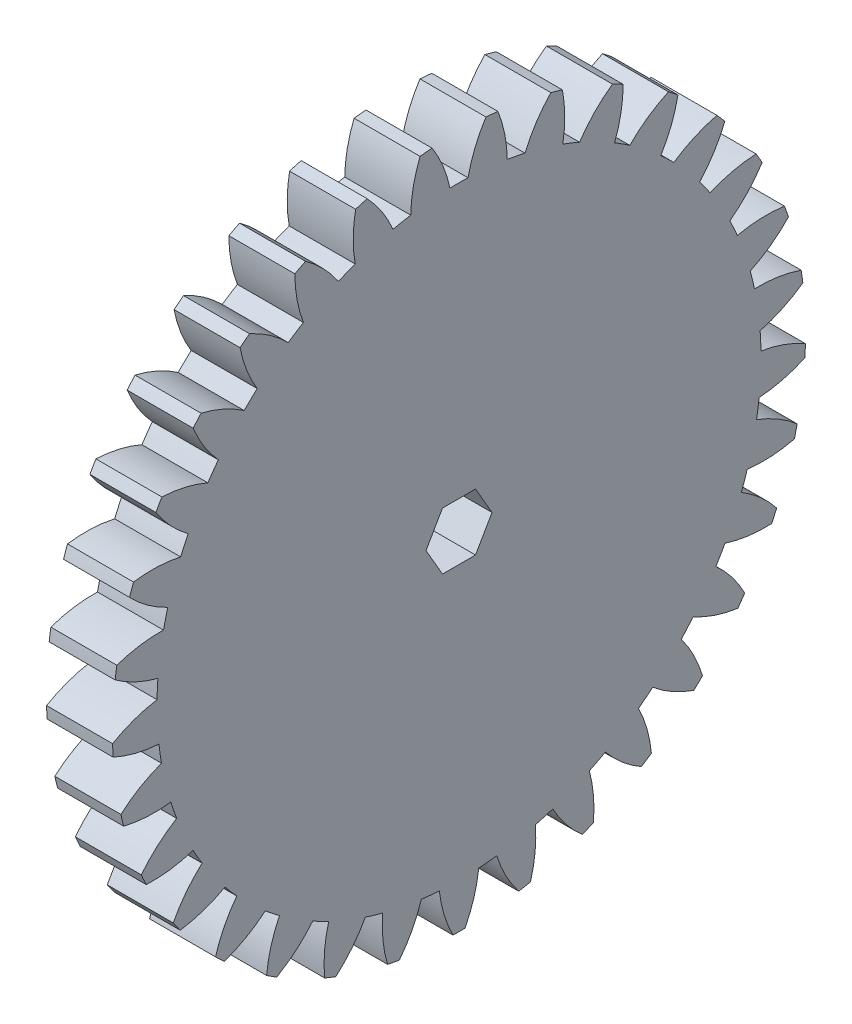
SolidWorks part; units mm, degrees
ref_plane "Plane1" through (0, 0, 0) normal (0, 0, 1) x (1, 0, 0)
ref_plane "Plane2" through (0, 0, 0) normal (0, 1, 0) x (1, 0, 0)
ref_plane "Plane3" through (0, 0, 0) normal (1, 0, 0) x (0, 0, -1)
sketch "HoldingSke" plane through (0, 0, 0) normal (0, 1, 0) x (1, 0, 0)
  line L0 (0, 0) -> (0.5591, -0.3631)
  line L1 (-15, 0) -> (100, 0) construction
  line L2 (0, 0) -> (-2.1039, 2.3779)
  line L3 (0, 0) -> (-11.863, 4.5341)
  line L4 (0, 0) -> (7.2428, 4.7035)
  line L5 (0, 0) -> (-46.8476, -17.4728)
  line L6 (0, 0) -> (-4.1448, -2.7965)
  line L7 (-2.1039, 2.3779) -> (8.6586, 51.2059)
  line L8 (-76.2, 54.61) -> (-75.3, 54.61)
  line L9 (-71.009, 38.7566) -> (-53.1078, 45.2721)
  line L10 (-76.2, 71.12) -> (104.1128, 71.12)
  line L11 (0, 0) -> (-5, 0)
  line L12 (-76.2, 101.6) -> (-76.147, 101.6)
  line L13 (24.9733, 27.94) -> (52.9518, 28.4284)
  line L14 (24.9733, 27.94) -> (24.9743, 27.94)
  line L15 (24.9733, 27.94) -> (100.4006, 29.5858)
  line L16 (-63.627, -1.5) -> (-12.827, -1.5)
  circle A0 centre (0, 0) radius 2.5
  circle A1 centre (0, 0) radius 22.874
  circle A2 centre (0, 0) radius 37.5
  circle A3 centre (0, 0) radius 2.5
  dimension "MHD" = 45.748
  dimension "Hub_dia" = 75
  dimension "Bore" = 5
  dimension "MBD" = 5
  dimension "Num_teeth" = 33
  dimension "Pitch" = 0.6667
  dimension "Overall_len" = 50
  dimension "Show_teeth" = 33
  dimension "Thickness" = 5
  dimension "OAL" = 50.0001
  dimension "T_dim" = 0.9
  dimension "Ap" = 20
  dimension "H" = 19.05
  dimension "Pitch_radius" = 180.3128
  dimension "Width" = 5
  dimension "Backlash" = 0.053
  dimension "Addendum_fac" = 1
  dimension "Dedendum_fac" = 1.25
  dimension "Clearance_fac" = 0.25
  dimension "Dedendum_add" = 0.001
  dimension "Module" = 1.5
sketch "BasProSke" plane through (0, 0, 0) normal (0, 1, 0) x (1, 0, 0)
  line L0 (-10, 0) -> (60, 0) construction
  line L1 (0, 0) -> (0, 26.25)
  line L2 (0, 0) -> (5, 0)
  line L3 (5, 0) -> (5, 26.25)
  line L4 (5, 26.25) -> (0, 26.25)
  dimension "Thickness" = 5
  dimension "Diameter" = 52.5
revolve "Base-Revolve" add sketch "BasProSke" angle 360 about L0
sketch "TooCutSke" plane through (0, 0, 0) normal (1, 0, 0) x (0, 0, -1)
  line L1 (0, 0) -> (0, 107) construction
  line L2 (0, 0) -> (-1.2704, 24.7174) construction
  line L3 (0, 0) -> (-4.7008, 49.2285) construction
  line L4 (-1.2704, 24.7174) -> (-2.3504, 24.6142) construction
  arc A0 (0.6837, 22.8638) -> (-0.6837, 22.8638) centre (0, 0) ccw
  arc A1 (2.0575, 26.1947) -> (-2.0575, 26.1947) centre (0, 0) ccw
  circle A2 centre (0, 0) radius 24.75 construction
  circle A3 centre (0, 0) radius 23.2574 construction
  arc A4 (-0.6837, 22.8638) -> (-2.0575, 26.1947) centre (-10.3699, 20.8176) ccw
  arc A5 (2.0575, 26.1947) -> (0.6837, 22.8638) centre (10.3699, 20.8176) ccw
  dimension "Root_dia" = 45.748
  dimension "Overcut_dia" = 52.5508
  dimension "Pitch_dia" = 49.5
  dimension "Base_dia" = 46.5148
  dimension "Flank_rad" = 9.9
  dimension "Half_ang" = 5.455
  dimension "Half_CT" = 1.0849
extrude "ToothCut" cut sketch "TooCutSke" along normal through all
fillet "Breaks" [suppressed] radius 0.03 tangent propagation no
fillet "RootFillets" [suppressed] radius 0.376
pattern_circular "TeethCuts" count 33 every 10.909 about axis through (-10, 0, 0) along (1, 0, 0) of "ToothCut", "RootFillets", "Breaks"
sketch "HubNeaOneSke" plane through (0, 0, 0) normal (-1, 0, 0) x (0, 0, 1)
  circle A0 centre (0, 0) radius 22.874
  dimension "Diameter" = 45.748
extrude "HubNearOne" [suppressed] add sketch "HubNeaOneSke" along normal blind 45.0001
sketch "HubNeaBotSke" plane through (0, 0, 0) normal (-1, 0, 0) x (0, 0, 1)
  circle A0 centre (0, 0) radius 22.874
  dimension "Diameter" = 45.748
extrude "HubNearBoth" [suppressed] add sketch "HubNeaBotSke" along normal blind 22.5
ref_plane "FarPln" through (5, 0, 0) normal (1, 0, 0) x (0, 0, -1)
sketch "HubFarSke" plane through (5, 0, 0) normal (1, 0, 0) x (0, 0, -1)
  circle A0 centre (0, 0) radius 22.874
  dimension "Diameter" = 45.748
extrude "HubFar" [suppressed] add sketch "HubFarSke" along normal blind 22.5
sketch "BorSke" plane through (0, 0, 0) normal (1, 0, 0) x (0, 0, -1)
  line L1 (-2.5, 0) -> (-1.25, -2.1651)
  line L2 (-1.25, -2.1651) -> (1.25, -2.1651)
  line L3 (1.25, -2.1651) -> (2.5, 0)
  line L4 (2.5, 0) -> (1.25, 2.1651)
  line L5 (1.25, 2.1651) -> (-1.25, 2.1651)
  line L6 (-1.25, 2.1651) -> (-2.5, 0)
  circle A0 centre (0, 0) radius 2.5 construction
  circle A1 centre (0, 0) radius 2.1651 construction
  point P2 (-2.5, 0)
  dimension "Diameter" = 5
extrude "Bore" cut sketch "BorSke" along normal mid plane 100.0001
sketch "KeySke" plane through (0, 0, 0) normal (1, 0, 0) x (0, 0, -1)
  line L0 (-1, 0) -> (-1, 3.4)
  line L1 (-1, 3.4) -> (1, 3.4)
  line L2 (1, 3.4) -> (1, 0)
  line L3 (0, 0) -> (0, 34) construction
  line L4 (-1, 0) -> (1, 0)
  dimension "Offset" = 3.4
  dimension "Width" = 2
extrude "Keyway" [suppressed] cut sketch "KeySke" along normal mid plane 100.0001
pattern_circular "Keyway2" [suppressed] count 2 every 90 about axis through (-10, 0, 0) along (1, 0, 0) reverse direction yes
sketch "Sketch1" plane through (0, 0, 0) normal (-1, 0, 0) x (0, 0, 1)
  line L0 (-1.25, -2.1651) -> (1.25, -2.1651) construction
  line L1 (-2.5, 0) -> (-1.25, -2.1651) construction
  line L2 (-1.25, 2.1651) -> (-2.5, 0) construction
  line L3 (1.25, 2.1651) -> (-1.25, 2.1651) construction
  line L4 (2.5, 0) -> (1.25, 2.1651) construction
  line L5 (1.25, -2.1651) -> (2.5, 0) construction
  line L6 (2.5, 0) -> (1.25, 2.1651)
  line L7 (1.25, 2.1651) -> (-1.25, 2.1651)
  line L8 (-1.25, 2.1651) -> (-2.5, 0)
  line L9 (-2.5, 0) -> (-1.25, -2.1651)
  line L10 (-1.25, -2.1651) -> (1.25, -2.1651)
  line L11 (1.25, -2.1651) -> (2.5, 0)
  arc A40 (0.1868, -8.9981) -> (0.8757, -5.5554) centre (-1.8542, -6.7994) ccw
  arc A41 (-0.1868, -8.9981) -> (0.1868, -8.9981) centre (0, 0) ccw
  arc A42 (-0.8757, -5.5554) -> (-0.1868, -8.9981) centre (1.8542, -6.7994) ccw
  arc A43 (-2.5569, -5.0091) -> (-0.8757, -5.5554) centre (0, 0) ccw
  arc A44 (-5.1378, -7.3894) -> (-2.5569, -5.0091) centre (-5.4967, -4.4109) ccw
  arc A45 (-5.4401, -7.1698) -> (-5.1378, -7.3894) centre (0, 0) ccw
  arc A46 (-3.9738, -3.9797) -> (-5.4401, -7.1698) centre (-2.4965, -6.5907) ccw
  arc A47 (-5.0129, -2.5496) -> (-3.9738, -3.9797) centre (0, 0) ccw
  arc A48 (-8.4999, -2.9582) -> (-5.0129, -2.5496) centre (-7.0396, -0.3377) ccw
  arc A49 (-8.6154, -2.6029) -> (-8.4999, -2.9582) centre (0, 0) ccw
  arc A50 (-5.5541, -0.8839) -> (-8.6154, -2.6029) centre (-5.8936, -3.8646) ccw
  arc A51 (-5.5541, 0.8839) -> (-5.5541, -0.8839) centre (0, 0) ccw
  arc A52 (-8.6154, 2.6029) -> (-5.5541, 0.8839) centre (-5.8936, 3.8646) ccw
  arc A53 (-8.4999, 2.9582) -> (-8.6154, 2.6029) centre (0, 0) ccw
  arc A54 (-5.0129, 2.5496) -> (-8.4999, 2.9582) centre (-7.0396, 0.3377) ccw
  arc A55 (-3.9738, 3.9797) -> (-5.0129, 2.5496) centre (0, 0) ccw
  arc A56 (-5.4401, 7.1698) -> (-3.9738, 3.9797) centre (-2.4965, 6.5907) ccw
  arc A57 (-5.1378, 7.3894) -> (-5.4401, 7.1698) centre (0, 0) ccw
  arc A58 (-2.5569, 5.0091) -> (-5.1378, 7.3894) centre (-5.4967, 4.4109) ccw
  arc A59 (-0.8757, 5.5554) -> (-2.5569, 5.0091) centre (0, 0) ccw
  arc A60 (-0.1868, 8.9981) -> (-0.8757, 5.5554) centre (1.8542, 6.7994) ccw
  arc A61 (0.1868, 8.9981) -> (-0.1868, 8.9981) centre (0, 0) ccw
  arc A62 (0.8757, 5.5554) -> (0.1868, 8.9981) centre (-1.8542, 6.7994) ccw
  arc A63 (2.5569, 5.0091) -> (0.8757, 5.5554) centre (0, 0) ccw
  arc A64 (5.1378, 7.3894) -> (2.5569, 5.0091) centre (5.4967, 4.4109) ccw
  arc A65 (5.4401, 7.1698) -> (5.1378, 7.3894) centre (0, 0) ccw
  arc A66 (3.9738, 3.9797) -> (5.4401, 7.1698) centre (2.4965, 6.5907) ccw
  arc A67 (5.0129, 2.5496) -> (3.9738, 3.9797) centre (0, 0) ccw
  arc A68 (8.4999, 2.9582) -> (5.0129, 2.5496) centre (7.0396, 0.3377) ccw
  arc A69 (8.6154, 2.6029) -> (8.4999, 2.9582) centre (0, 0) ccw
  arc A70 (5.5541, 0.8839) -> (8.6154, 2.6029) centre (5.8936, 3.8646) ccw
  arc A71 (5.5541, -0.8839) -> (5.5541, 0.8839) centre (0, 0) ccw
  arc A72 (8.6154, -2.6029) -> (5.5541, -0.8839) centre (5.8936, -3.8646) ccw
  arc A73 (8.4999, -2.9582) -> (8.6154, -2.6029) centre (0, 0) ccw
  arc A74 (5.0129, -2.5496) -> (8.4999, -2.9582) centre (7.0396, -0.3377) ccw
  arc A75 (3.9738, -3.9797) -> (5.0129, -2.5496) centre (0, 0) ccw
  arc A76 (5.4401, -7.1698) -> (3.9738, -3.9797) centre (2.4965, -6.5907) ccw
  arc A77 (5.1378, -7.3894) -> (5.4401, -7.1698) centre (0, 0) ccw
  arc A78 (2.5569, -5.0091) -> (5.1378, -7.3894) centre (5.4967, -4.4109) ccw
  arc A79 (0.8757, -5.5554) -> (2.5569, -5.0091) centre (0, 0) ccw
  arc A80 (0.1868, -8.9981) -> (0.8757, -5.5554) centre (-1.8542, -6.7994) ccw
  arc A81 (-0.1868, -8.9981) -> (0.1868, -8.9981) centre (0, 0) ccw
  arc A82 (-0.8757, -5.5554) -> (-0.1868, -8.9981) centre (1.8542, -6.7994) ccw
  arc A83 (-2.5569, -5.0091) -> (-0.8757, -5.5554) centre (0, 0) ccw
  arc A84 (-5.1378, -7.3894) -> (-2.5569, -5.0091) centre (-5.4967, -4.4109) ccw
  arc A85 (-5.4401, -7.1698) -> (-5.1378, -7.3894) centre (0, 0) ccw
  arc A86 (-3.9738, -3.9797) -> (-5.4401, -7.1698) centre (-2.4965, -6.5907) ccw
  arc A87 (-5.0129, -2.5496) -> (-3.9738, -3.9797) centre (0, 0) ccw
  arc A88 (-8.4999, -2.9582) -> (-5.0129, -2.5496) centre (-7.0396, -0.3377) ccw
  arc A89 (-8.6154, -2.6029) -> (-8.4999, -2.9582) centre (0, 0) ccw
  arc A90 (-5.5541, -0.8839) -> (-8.6154, -2.6029) centre (-5.8936, -3.8646) ccw
  arc A91 (-5.5541, 0.8839) -> (-5.5541, -0.8839) centre (0, 0) ccw
  arc A92 (-8.6154, 2.6029) -> (-5.5541, 0.8839) centre (-5.8936, 3.8646) ccw
  arc A93 (-8.4999, 2.9582) -> (-8.6154, 2.6029) centre (0, 0) ccw
  arc A94 (-5.0129, 2.5496) -> (-8.4999, 2.9582) centre (-7.0396, 0.3377) ccw
  arc A95 (-3.9738, 3.9797) -> (-5.0129, 2.5496) centre (0, 0) ccw
  arc A96 (-5.4401, 7.1698) -> (-3.9738, 3.9797) centre (-2.4965, 6.5907) ccw
  arc A97 (-5.1378, 7.3894) -> (-5.4401, 7.1698) centre (0, 0) ccw
  arc A98 (-2.5569, 5.0091) -> (-5.1378, 7.3894) centre (-5.4967, 4.4109) ccw
  arc A99 (-0.8757, 5.5554) -> (-2.5569, 5.0091) centre (0, 0) ccw
  arc A100 (-0.1868, 8.9981) -> (-0.8757, 5.5554) centre (1.8542, 6.7994) ccw
  arc A101 (0.1868, 8.9981) -> (-0.1868, 8.9981) centre (0, 0) ccw
  arc A102 (0.8757, 5.5554) -> (0.1868, 8.9981) centre (-1.8542, 6.7994) ccw
  arc A103 (2.5569, 5.0091) -> (0.8757, 5.5554) centre (0, 0) ccw
  arc A104 (5.1378, 7.3894) -> (2.5569, 5.0091) centre (5.4967, 4.4109) ccw
  arc A105 (5.4401, 7.1698) -> (5.1378, 7.3894) centre (0, 0) ccw
  arc A106 (3.9738, 3.9797) -> (5.4401, 7.1698) centre (2.4965, 6.5907) ccw
  arc A107 (5.0129, 2.5496) -> (3.9738, 3.9797) centre (0, 0) ccw
  arc A108 (8.4999, 2.9582) -> (5.0129, 2.5496) centre (7.0396, 0.3377) ccw
  arc A109 (8.6154, 2.6029) -> (8.4999, 2.9582) centre (0, 0) ccw
  arc A110 (5.5541, 0.8839) -> (8.6154, 2.6029) centre (5.8936, 3.8646) ccw
  arc A111 (5.5541, -0.8839) -> (5.5541, 0.8839) centre (0, 0) ccw
  arc A112 (8.6154, -2.6029) -> (5.5541, -0.8839) centre (5.8936, -3.8646) ccw
  arc A113 (8.4999, -2.9582) -> (8.6154, -2.6029) centre (0, 0) ccw
  arc A114 (5.0129, -2.5496) -> (8.4999, -2.9582) centre (7.0396, -0.3377) ccw
  arc A115 (3.9738, -3.9797) -> (5.0129, -2.5496) centre (0, 0) ccw
  arc A116 (5.4401, -7.1698) -> (3.9738, -3.9797) centre (2.4965, -6.5907) ccw
  arc A117 (5.1378, -7.3894) -> (5.4401, -7.1698) centre (0, 0) ccw
  arc A118 (2.5569, -5.0091) -> (5.1378, -7.3894) centre (5.4967, -4.4109) ccw
  arc A119 (0.8757, -5.5554) -> (2.5569, -5.0091) centre (0, 0) ccw
  dimension "D1" = 0
extrude "Boss-Extrude1" add sketch "Sketch1" along normal blind 6
equation "' \"Module@HoldingSke\" = 6.35"
equation "' \"Num_teeth@HoldingSke\" = 12"
equation "' \"Ap@HoldingSke\" =  20"
equation "' \"Ap@HoldingSke\" = 20"
equation "' \"Width@HoldingSke\" = 0.5 * 25.4"
equation "' \"Hub_dia@HoldingSke\"= 1 * 25.4"
equation "' \"Hub_dia@HoldingSke\" = 1 * 25.4"
equation "' \"Overall_len@HoldingSke\" = 1.0 * 25.4"
equation "' \"Bore@HoldingSke\" = 0.75 * 25.4"
equation "' \"T_dim@HoldingSke\" = 0.1 * 25.4"
equation "' \"Width@KeySke\" = 0.25 * 25.4"
equation "' \"Show_teeth@HoldingSke\" = 13"
equation "' \"Backlash@HoldingSke\" = 0.009 * 25.4"
equation "' \"Addendum_fac@HoldingSke\" = 1.0"
equation "' \"Dedendum_fac@HoldingSke\" = 1.25"
equation "' \"Dedendum_add@HoldingSke\" = 0.00005 * 25.4"
equation "' \"Clearance_fac@HoldingSke\" = 0.25"
equation "\"Pitch@HoldingSke\" = 1 / \"Module@HoldingSke\""
equation "\"Overcut_dia@TooCutSke\" = (\"Num_teeth@HoldingSke\" + 2 * \"Addendum_fac@HoldingSke\") / \"Pitch@HoldingSke\" + 0.002 * 25.4"
equation "\"Pitch_dia@TooCutSke\" = \"Num_teeth@HoldingSke\" / \"Pitch@HoldingSke\""
equation "\"Base_dia@TooCutSke\" = \"Num_teeth@HoldingSke\" / \"Pitch@HoldingSke\" * cos((\"Ap@HoldingSke\"  * 3.14159265 / 180))"
equation "\"Root_dia@TooCutSke\" = (\"Num_teeth@HoldingSke\" + 2) / \"Pitch@HoldingSke\" - 2 * (\"Addendum_fac@HoldingSke\" + \"Dedendum_fac@HoldingSke\") / \"Pitch@HoldingSke\" - \"Dedendum_add@HoldingSke\" * 2"
equation "\"Half_ang@TooCutSke\" = 180 / \"Num_teeth@HoldingSke\""
equation "\"Half_CT@TooCutSke\" = \"Num_teeth@HoldingSke\" / \"Pitch@HoldingSke\" * sin((3.14159265 / 2 / \"Num_teeth@HoldingSke\")) / 2 - 7 * \"Backlash@HoldingSke\" / 4"
equation "\"Flank_rad@TooCutSke\" = \"Num_teeth@HoldingSke\" / \"Pitch@HoldingSke\" / 5"
equation "\"Radius@RootFillets\" = \"Clearance_fac@HoldingSke\" / \"Pitch@HoldingSke\" + \"Dedendum_add@HoldingSke\""
equation "\"Break_rad@Breaks\" = 0.02 / \"Pitch@HoldingSke\""
equation "\"Thickness@HoldingSke\" = \"Width@HoldingSke\""
equation "\"OAL@HoldingSke\" = \"Thickness@HoldingSke\""
equation "\"MHD@HoldingSke\" = (\"Num_teeth@HoldingSke\" + 2) / \"Pitch@HoldingSke\" - 2 * (\"Addendum_fac@HoldingSke\" + \"Dedendum_fac@HoldingSke\")  / \"Pitch@HoldingSke\" - \"Dedendum_add@HoldingSke\" * 2"
equation "\"MBD@HoldingSke\" = (\"Num_teeth@HoldingSke\" + 2) / \"Pitch@HoldingSke\" - 2 * (\"Addendum_fac@HoldingSke\" + \"Dedendum_fac@HoldingSke\")  / \"Pitch@HoldingSke\" - \"Dedendum_add@HoldingSke\" * 2 - 0.002 * 25.4"
equation "\"MHD@HoldingSke\" = ((sgn( \"MHD@HoldingSke\" - \"Hub_dia@HoldingSke\" )-1)*( \"MHD@HoldingSke\" - \"Hub_dia@HoldingSke\" ))/-2+ \"Hub_dia@HoldingSke\""
equation "\"MBD@HoldingSke\" = ((sgn( \"MBD@HoldingSke\" - \"Bore@HoldingSke\" )-1)*( \"MBD@HoldingSke\" - \"Bore@HoldingSke\" ))/-2+ \"Bore@HoldingSke\""
equation "\"OAL@HoldingSke\" = ((sgn( \"OAL@HoldingSke\" - \"Overall_len@HoldingSke\" )+1)*( \"OAL@HoldingSke\" - \"Overall_len@HoldingSke\" ))/2 + \"Overall_len@HoldingSke\" + 0.000002 * 25.4"
equation "\"Num_teeth@TeethCuts\" = int( \"Show_teeth@HoldingSke\" ) + 1"
equation "\"Num_teeth@TeethCuts\" = ((sgn( \"Num_teeth@TeethCuts\" - \"Num_teeth@HoldingSke\" )-1)*( \"Num_teeth@TeethCuts\" - \"Num_teeth@HoldingSke\" ))/-2+ \"Num_teeth@HoldingSke\""
equation "\"Num_teeth@TeethCuts\" = ((sgn( \"Num_teeth@TeethCuts\" - 2.0)+1)*( \"Num_teeth@TeethCuts\" - 2.0))/2 +2.0"
equation "\"Angle@TeethCuts\" = 360.0 / \"Num_teeth@HoldingSke\""
equation "\"Diameter@BasProSke\" = (\"Num_teeth@HoldingSke\" + 2 * \"Addendum_fac@HoldingSke\") / \"Pitch@HoldingSke\""
equation "\"Thickness@BasProSke\"  = \"Thickness@HoldingSke\""
equation "' \"Fillet_rad@BasProSke\" =  \"Thickness@HoldingSke\" * 0.05"
equation "' \"Fillet_rad@BasProSke\" = \"Thickness@HoldingSke\" * 0.05"
equation "\"MHD@HoldingSke\" = ((sgn( \"MHD@HoldingSke\" - \"Root_dia@TooCutSke\" )-1)*( \"MHD@HoldingSke\" - \"Root_dia@TooCutSke\" ))/-2+ \"Root_dia@TooCutSke\""
equation "\"Diameter@HubNeaOneSke\" = \"MHD@HoldingSke\""
equation "\"Length@HubNearOne\" = \"OAL@HoldingSke\" - \"Thickness@BasProSke\""
equation "\"Diameter@HubNeaBotSke\" = \"MHD@HoldingSke\""
equation "\"Length@HubNearBoth\" = ( \"OAL@HoldingSke\" - \"Thickness@BasProSke\" ) / 2.0"
equation "\"Thickness@FarPln\" = \"Thickness@BasProSke\""
equation "\"Diameter@HubFarSke\" = \"MHD@HoldingSke\""
equation "\"Length@HubFar\" = ( \"OAL@HoldingSke\" - \"Thickness@BasProSke\" ) / 2.0"
equation "\"Diameter@BorSke\" = \"MBD@HoldingSke\""
equation "\"D1@Bore\" = \"OAL@HoldingSke\" * 2.0"
equation "\"D1@Keyway\" = \"OAL@HoldingSke\" * 2.0"
equation "\"Offset@KeySke\" = \"T_dim@HoldingSke\" + \"MBD@HoldingSke\" / 2.0"
